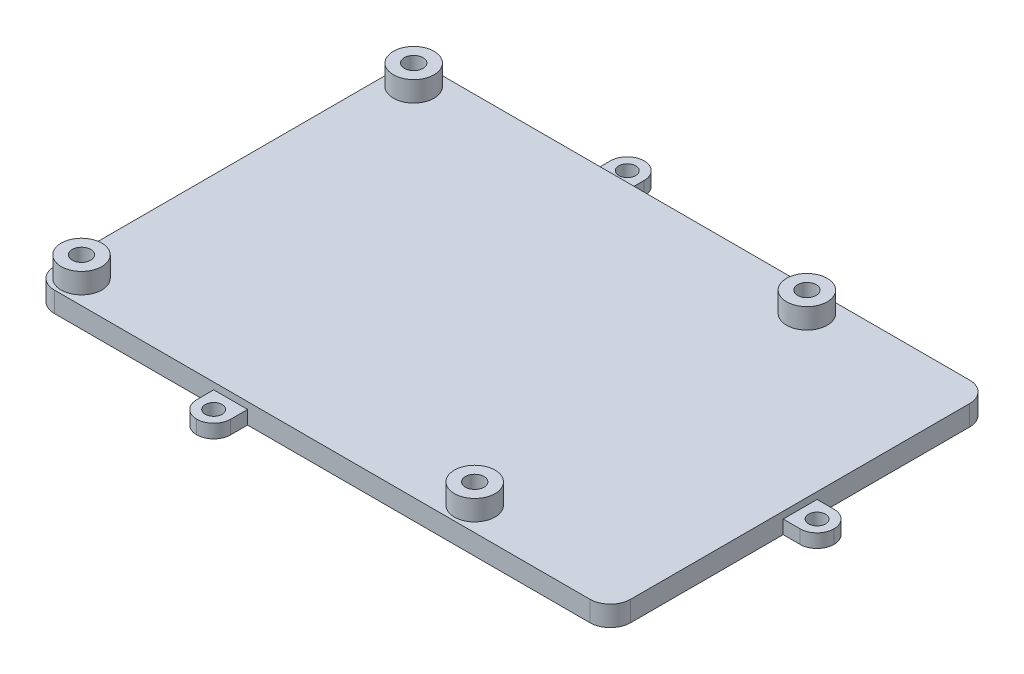
SolidWorks part; units mm, degrees
ref_plane "Front Plane" through (0, 0, 0) normal (0, 0, 1) x (1, 0, 0)
ref_plane "Top Plane" through (0, 0, 0) normal (0, 1, 0) x (1, 0, 0)
ref_plane "Right Plane" through (0, 0, 0) normal (1, 0, 0) x (0, 0, -1)
sketch "Sketch1" plane through (0, 0, 0) normal (0, 1, 0) x (1, 0, 0)
  line L1 (0, 56) -> (85, 56)
  line L2 (0, 56) -> (0, 0)
  line L3 (0, 0) -> (85, 0)
  line L4 (85, 56) -> (85, 0)
  circle A0 centre (3.5, 52.5) radius 1.375
  circle A1 centre (61.5, 52.5) radius 1.375
  circle A2 centre (3.5, 3.5) radius 1.375
  circle A3 centre (61.5, 3.5) radius 1.375
  dimension "D3" = 2.75
  dimension "D4" = 2.75
  dimension "D5" = 2.75
  dimension "D6" = 2.75
  dimension "D1" = 85
  dimension "D2" = 56
  dimension "D7" = 49
  dimension "D8" = 58
  dimension "D10" = 3.5
  dimension "D11" = 3.5
extrude "Boss-Extrude1" add sketch "Sketch1" along normal blind 3
fillet "Fillet1" radius 3 4 edges at (0, 1.5, -56) (85, 1.5, -56) (85, 1.5, 0) (0, 1.5, 0)
sketch "Sketch3" plane through (0, 3, 0) normal (0, 1, 0) x (1, 0, 0)
  circle A0 centre (3.5, 52.5) radius 3
  circle A1 centre (61.5, 52.5) radius 3
  circle A2 centre (3.5, 3.5) radius 3
  circle A3 centre (61.5, 3.5) radius 3
  circle A4 centre (3.5, 52.5) radius 1.375
  circle A5 centre (61.5, 52.5) radius 1.375
  circle A6 centre (61.5, 3.5) radius 1.375
  circle A7 centre (3.5, 3.5) radius 1.375
  dimension "D1" = 6
  dimension "D2" = 6
  dimension "D3" = 6
  dimension "D4" = 6
  dimension "D5" = 2.75
  dimension "D6" = 2.75
  dimension "D7" = 2.75
  dimension "D8" = 2.75
extrude "Boss-Extrude3" add sketch "Sketch3" along normal blind 3
sketch "Sketch5" plane through (0, 0, 0) normal (0, -1, 0) x (1, 0, 0)
  line L0 (3, 0) -> (82, 0) construction
  line L1 (26.5, 0) -> (31.5, 0)
  line L2 (26.5, 0) -> (26.5, 5)
  line L3 (26.5, 5) -> (31.5, 5)
  line L4 (31.5, 0) -> (31.5, 5)
  line L5 (0, -53) -> (0, -3) construction
  circle A0 centre (29, 2.5) radius 1.25
  point P8 (29, 0)
  dimension "D4" = 2.5
  dimension "D1" = 5
  dimension "D2" = 5
  dimension "D3" = 29
  dimension "D5" = 2.5
  dimension "D6" = 2.5
extrude "Boss-Extrude4" add sketch "Sketch5" against normal blind 2
fillet "Fillet2" radius 2.5 2 edges at (26.5, 1, 5) (31.5, 1, 5)
sketch "Sketch6" plane through (0, 0, 0) normal (0, -1, 0) x (1, 0, 0)
  line L0 (82, -56) -> (3, -56) construction
  line L1 (26.5, -56) -> (31.5, -56)
  line L2 (26.5, -56) -> (26.5, -61)
  line L3 (26.5, -61) -> (31.5, -61)
  line L4 (31.5, -56) -> (31.5, -61)
  line L5 (0, -53) -> (0, -3) construction
  circle A0 centre (29, -58.5) radius 1.25
  point P8 (29, -56)
  dimension "D4" = 2.5
  dimension "D1" = 5
  dimension "D2" = 5
  dimension "D3" = 29
  dimension "D5" = 2.5
  dimension "D6" = 2.5
extrude "Boss-Extrude5" add sketch "Sketch6" against normal blind 2
fillet "Fillet3" radius 2.5 2 edges at (31.5, 1, -61) (26.5, 1, -61)
sketch "Sketch8" plane through (0, 0, 0) normal (0, -1, 0) x (1, 0, 0)
  line L0 (85, -3) -> (85, -53) construction
  line L1 (85, -25.5) -> (90, -25.5)
  line L2 (85, -25.5) -> (85, -30.5)
  line L3 (85, -30.5) -> (90, -30.5)
  line L4 (90, -25.5) -> (90, -30.5)
  line L5 (31.5, 0) -> (82, 0) construction
  circle A0 centre (87.5, -28) radius 1.25
  point P8 (85, -28)
  dimension "D4" = 2.5
  dimension "D1" = 5
  dimension "D2" = 5
  dimension "D3" = 28
  dimension "D5" = 2.5
  dimension "D6" = 2.5
extrude "Boss-Extrude7" add sketch "Sketch8" against normal blind 2
fillet "Fillet5" radius 2.5 2 edges at (90, 1, -30.5) (90, 1, -25.5)
